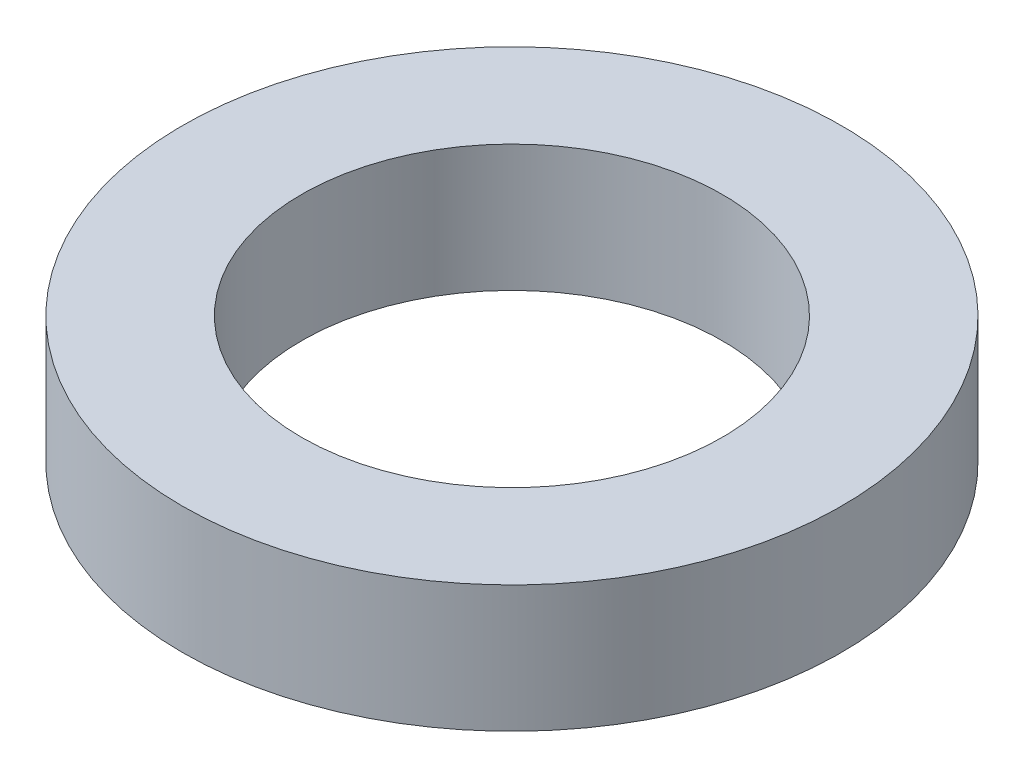
SolidWorks part; units mm, degrees
ref_plane "Front Plane" through (0, 0, 0) normal (0, 0, 1) x (1, 0, 0)
ref_plane "Top Plane" through (0, 0, 0) normal (0, 1, 0) x (1, 0, 0)
ref_plane "Right Plane" through (0, 0, 0) normal (1, 0, 0) x (0, 0, -1)
ref_axis "Axis1" through (0, 0, 0) along (0, 1, 0)
sketch "Sketch1" plane through (0, 0, 0) normal (0, 0, 1) x (1, 0, 0)
  line L0 (0, 0) -> (0, -50000) construction
  line L1 (-6.5, 2.5) -> (-4.15, 2.5)
  line L2 (-6.5, 2.5) -> (-6.5, 0)
  line L3 (-6.5, 0) -> (-4.15, 0)
  line L4 (-4.15, 2.5) -> (-4.15, 0)
  dimension "D1" = 2.5
  dimension "D2" = 13
  dimension "D3" = 8.3
revolve "Revolve1" add sketch "Sketch1" angle 360 about L0
